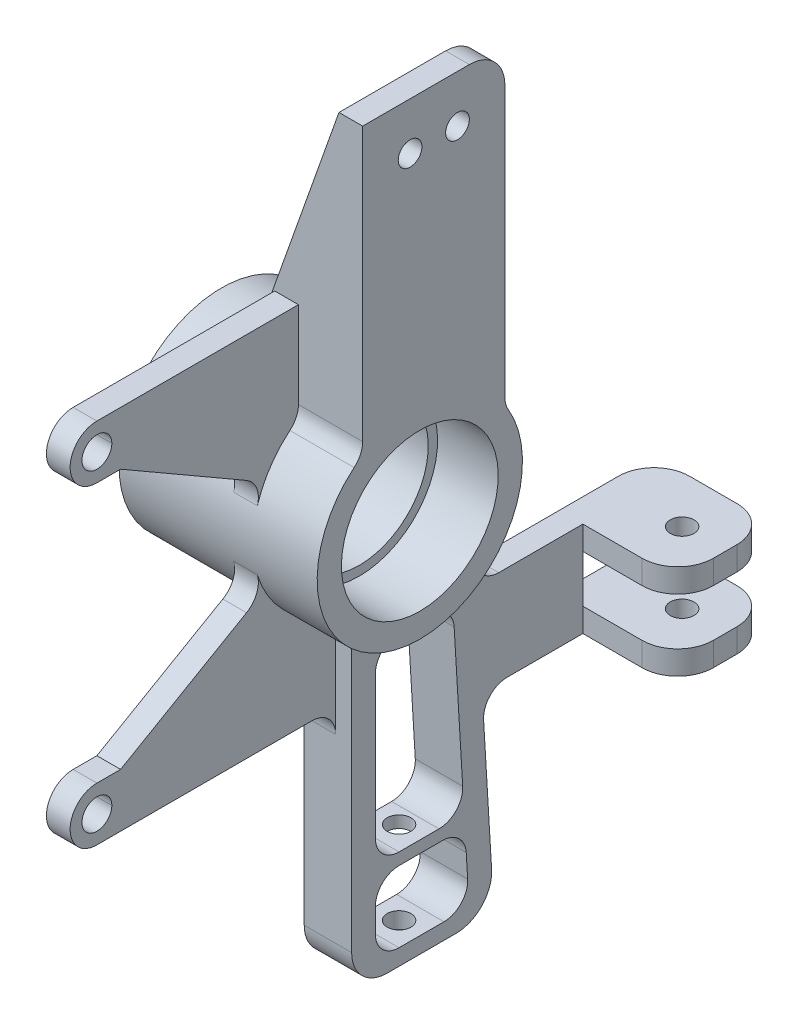
SolidWorks part; units mm, degrees
ref_plane "Front Plane" through (0, 0, 0) normal (0, 0, 1) x (1, 0, 0)
ref_plane "Top Plane" through (0, 0, 0) normal (0, 1, 0) x (1, 0, 0)
ref_plane "Right Plane" through (0, 0, 0) normal (1, 0, 0) x (0, 0, -1)
sketch "Sketch1" plane through (0, 0, 0) normal (0, 0, 1) x (1, 0, 0)
  line L0 (0, 0) -> (53.0908, 0) construction
  line L1 (0, 23.5) -> (16.2791, 23.5)
  line L2 (16.2791, 23.5) -> (16.2791, 18.5)
  line L3 (16.2791, 18.5) -> (36.8482, 18.5)
  line L4 (36.8482, 18.5) -> (36.8482, 21)
  line L5 (36.8482, 21) -> (53.0908, 21)
  line L6 (16.2791, 23.5) -> (16.2791, 0) construction
  line L7 (0, 23.5) -> (0, 0) construction
  line L8 (36.8482, 21) -> (36.8482, 0) construction
  line L9 (53.0908, 21) -> (53.0908, 0) construction
  line L10 (44.9695, 0) -> (61.4795, 0) construction
  line L11 (0, 11.75) -> (16.2791, 11.75) construction
  line L12 (36.8482, 10.5) -> (53.0908, 10.5) construction
  line L13 (0, 23.5) -> (0, 27.5)
  line L14 (0, 27.5) -> (53.0908, 27.5)
  line L15 (53.0908, 27.5) -> (53.0908, 21)
  point P11 (36.8482, 10.5)
  point P19 (8.1395, 11.75)
  point P20 (44.9695, 10.5)
  dimension "D1" = 21
  dimension "D2" = 23.5
  dimension "D3" = 16.2791
  dimension "D4" = 16.2426
  dimension "D5" = 36.83
  dimension "D6" = 4
  dimension "D7" = 2.5
  dimension "D8" = 16.51
revolve "Revolve1" add sketch "Sketch1" angle 360 about L0
sketch "Sketch2" plane through (53.0908, 0, 0) normal (1, 0, 0) x (0, 0, -1)
  line L0 (22.7917, 99.2079) -> (22.7917, 15.3879)
  line L1 (22.7917, 99.2079) -> (-15.3083, 99.2079)
  line L2 (-15.3083, 99.2079) -> (-15.3083, 22.8453)
  line L4 (-1525.5875, -203.2) -> (0, -203.2) construction
  circle A0 centre (0, 0) radius 27.5 construction
  arc A3 (22.7917, 15.3879) -> (-15.3083, 22.8453) centre (0, 0) ccw
  point P4 (3.7417, 99.2079)
  dimension "D1" = 83.82
  dimension "D2" = 38.1
extrude "Boss-Extrude1" add sketch "Sketch2" against normal blind 6.35
ref_plane "Plane1" through (33.8016, 0, 0) normal (1, 0, 0) x (0, 0, -1)
sketch "Sketch4" plane through (33.8016, 0, 0) normal (1, 0, 0) x (0, 0, -1)
  line L3 (0, 0) -> (13.7254, -101.6) construction
  line L4 (26.4254, -7.6125) -> (32.7754, -113.538)
  line L10 (-5.3246, -26.9796) -> (-5.3246, -113.538)
  line L15 (-5.3246, -113.538) -> (32.7754, -113.538)
  circle A0 centre (0, 0) radius 27.5 construction
  arc A1 (-5.3246, -26.9796) -> (26.4254, -7.6125) centre (0, 0) ccw
  point P3 (13.7254, -113.538)
  dimension "D1" = 11.938
  dimension "D2" = 38.1
  dimension "D7" = 31.75
extrude "Boss-Extrude2" add sketch "Sketch4" against normal blind 6.35 and the other way blind 6.35
sketch "Sketch5" plane through (40.1516, 0, 0) normal (1, 0, 0) x (0, 0, -1)
  line L0 (29.6234, -60.96) -> (82.0236, -60.96)
  line L2 (82.0236, -60.96) -> (82.0236, -54.61)
  line L3 (82.0236, -54.61) -> (56.6236, -54.61)
  line L4 (56.6236, -54.61) -> (56.6236, -41.91)
  line L5 (56.6236, -41.91) -> (82.0236, -41.91)
  line L6 (82.0236, -41.91) -> (82.0236, -35.56)
  line L7 (82.0236, -35.56) -> (28.1008, -35.56)
  line L9 (32.7754, -113.538) -> (26.4254, -7.6125) construction
  line L10 (28.1008, -35.56) -> (29.6234, -60.96)
  point P2 (69.3236, -54.61)
  point P10 (56.6236, -48.26)
  dimension "D1" = 6.35
  dimension "D2" = 25.4
  dimension "D3" = 12.7
extrude "Boss-Extrude3" add sketch "Sketch5" against normal blind 6.35
sketch "Sketch6" plane through (40.1516, 0, 0) normal (1, 0, 0) x (0, 0, -1)
  line L0 (82.0236, -54.61) -> (56.6236, -54.61) construction
  line L1 (82.0236, -35.56) -> (56.6236, -35.56)
  line L2 (82.0236, -35.56) -> (82.0236, -41.91)
  line L3 (82.0236, -41.91) -> (56.6236, -41.91)
  line L4 (56.6236, -35.56) -> (56.6236, -41.91)
  line L5 (82.0236, -60.96) -> (56.6236, -60.96)
  line L6 (82.0236, -60.96) -> (82.0236, -54.61)
  line L7 (82.0236, -54.61) -> (56.6236, -54.61)
  line L8 (56.6236, -60.96) -> (56.6236, -54.61)
  line L9 (56.6236, -54.61) -> (56.6236, -41.91) construction
extrude "Boss-Extrude4" add sketch "Sketch6" along normal blind 25.4
sketch "Sketch7" plane through (46.7408, 0, 0) normal (-1, 0, 0) x (0, 0, 1)
  line L0 (15.3083, 22.8453) -> (15.3083, 99.2079)
  line L1 (15.3083, 99.2079) -> (15.3083, 22.8453) construction
  line L2 (15.3083, 99.2079) -> (8.9583, 99.2079)
  line L3 (8.9583, 99.2079) -> (8.9583, 26)
  line L4 (-22.7917, 99.2079) -> (15.3083, 99.2079) construction
  circle A0 centre (0, 0) radius 27.5 construction
  arc A1 (15.3083, 22.8453) -> (-22.7917, 15.3879) centre (0, 0) ccw construction
  arc A2 (15.3083, 22.8453) -> (8.9583, 26) centre (0, 0) ccw
  dimension "D1" = 6.35
extrude "Boss-Extrude5" add sketch "Sketch7" along normal blind 25.4
sketch "Sketch8" plane through (35.8795, 0, 0) normal (-1, 0, 0) x (0, 0, 1)
  line L0 (15.3083, 22.8453) -> (15.3083, 99.2079) construction
  line L1 (15.3083, 49.175) -> (69.3, 49.175)
  line L4 (15.3083, 22.8453) -> (15.3083, 49.175)
  line L5 (69.3, 42) -> (76.475, 42) construction
  line L7 (24.4463, 12.5949) -> (62.95, 34.825)
  line L8 (62.95, 34.825) -> (69.3, 34.825)
  arc A0 (69.3, 38) -> (69.3, 46) centre (69.3, 42) ccw construction
  arc A1 (69.3, 46) -> (69.3, 38) centre (69.3, 42) ccw construction
  arc A2 (69.3, 38) -> (69.3, 46) centre (69.3, 42) ccw
  arc A3 (69.3, 46) -> (69.3, 38) centre (69.3, 42) ccw
  circle A4 centre (0, 0) radius 27.5 construction
  arc A6 (69.3, 34.825) -> (69.3, 49.175) centre (69.3, 42) ccw
  arc A14 (24.4463, 12.5949) -> (15.3083, 22.8453) centre (0, 0) ccw
  dimension "D1" = 3.175
  dimension "D2" = 30
  dimension "D3" = 6.35
extrude "Boss-Extrude6" add sketch "Sketch8" along normal blind 6.35
sketch "Sketch9" plane through (35.8795, 0, 0) normal (-1, 0, 0) x (0, 0, 1)
  line L0 (5.3246, -49.175) -> (69.3, -49.175)
  line L1 (5.3246, -26.9796) -> (5.3246, -113.538) construction
  line L3 (5.3246, -49.175) -> (5.3246, -26.9796)
  line L5 (69.3, -34.825) -> (62.95, -34.825)
  line L6 (62.95, -34.825) -> (24.4463, -12.5949)
  line L7 (69.3, -42) -> (76.475, -42) construction
  arc A0 (69.3, -46) -> (69.3, -38) centre (69.3, -42) ccw construction
  arc A1 (69.3, -38) -> (69.3, -46) centre (69.3, -42) ccw construction
  arc A2 (69.3, -46) -> (69.3, -38) centre (69.3, -42) ccw
  arc A3 (69.3, -38) -> (69.3, -46) centre (69.3, -42) ccw
  arc A4 (69.3, -49.175) -> (69.3, -34.825) centre (69.3, -42) ccw
  circle A5 centre (0, 0) radius 27.5 construction
  arc A7 (5.3246, -26.9796) -> (24.4463, -12.5949) centre (0, 0) ccw
  dimension "D1" = 3.175
  dimension "D3" = 6.35
  dimension "D2" = 30
sketch "Sketch10" plane through (0, 0, 8.9583) normal (0, 0, -1) x (-1, 0, 0)
  line L0 (-46.7408, 99.2079) -> (-21.3408, 27.5)
  line L1 (-21.3408, 99.2079) -> (-21.3408, 26) construction
  line L2 (-21.3408, 27.5) -> (-21.3408, 99.2079)
  line L3 (-21.3408, 99.2079) -> (-46.7408, 99.2079)
  line L4 (0, 27.5) -> (-53.0908, 27.5) construction
extrude "Cut-Extrude1" cut sketch "Sketch10" against normal up to next
sketch "Sketch13" plane through (40.1516, 0, 0) normal (1, 0, 0) x (0, 0, -1)
  line L0 (26.1551, -109.22) -> (25.0131, -90.17)
  line L1 (25.0131, -90.17) -> (1.0254, -90.17)
  line L2 (1.0254, -90.17) -> (1.0254, -109.22)
  line L3 (1.0254, -109.22) -> (26.1551, -109.22)
  line L4 (21.7774, -36.195) -> (24.8228, -86.995)
  line L5 (24.8228, -86.995) -> (1.0254, -86.995)
  line L6 (1.0254, -86.995) -> (1.0254, -36.195)
  line L7 (1.0254, -36.195) -> (21.7774, -36.195)
  line L8 (32.7754, -113.538) -> (29.6234, -60.96) construction
  line L9 (-5.3246, -26.9796) -> (-5.3246, -113.538) construction
  dimension "D1" = 6.35
  dimension "D2" = 6.35
  dimension "D3" = 3.175
  dimension "D4" = 7.62
  dimension "D5" = 19.05
  dimension "D6" = 50.8
extrude "Cut-Extrude2" cut sketch "Sketch13" against normal up to next
sketch "Sketch14" plane through (0, -86.995, 0) normal (0, 1, 0) x (1, 0, 0)
  circle A0 centre (33.8016, 13.7254) radius 3.175
  dimension "D1" = 6.35
extrude "Cut-Extrude3" cut sketch "Sketch14" against normal through all
sketch "Sketch15" plane through (53.0908, 0, 0) normal (1, 0, 0) x (0, 0, -1)
  line L0 (-2.6083, 86.5079) -> (10.0917, 86.5079) construction
  line L1 (22.7917, 99.2079) -> (-15.3083, 99.2079) construction
  circle A0 centre (-2.6083, 86.5079) radius 3.175
  circle A1 centre (10.0917, 86.5079) radius 3.175
  point P6 (3.7417, 99.2079)
  point P7 (3.7417, 86.5079)
  dimension "D1" = 6.35
  dimension "D3" = 12.7
  dimension "D2" = 12.7
extrude "Cut-Extrude4" cut sketch "Sketch15" against normal up to next
sketch "Sketch16" plane through (0, -35.56, 0) normal (0, 1, 0) x (1, 0, 0)
  circle A0 centre (54.033, 69.3236) radius 3.175
  dimension "D1" = 6.35
extrude "Cut-Extrude5" cut sketch "Sketch16" against normal through all
extrude "Boss-Extrude7" add sketch "Sketch9" along normal blind 6.35
fillet "0.375 Fillet1" radius 9.525 9 edges at (33.8016, -113.538, 5.3246) (33.8016, -113.538, -32.7754) (49.9158, 99.2079, -22.7917) (65.5516, -57.785, -82.0236) (65.5516, -57.785, -56.6236) (65.5516, -38.735, -56.6236) (65.5516, -38.735, -82.0236) (33.8016, -57.785, -82.0236) (33.8016, -38.735, -82.0236)
fillet "0.25 Fillet1" radius 6.35 18 edges at (36.9766, -60.96, -29.6234) (36.9766, -35.56, -28.1008) (34.0408, 26, 8.9583) (33.8016, -7.6125, -26.4254) (49.9158, 15.3879, -22.7917) (44.4852, 22.8453, 15.3083) (25.4352, 22.8453, 15.3083) (32.7045, 12.5949, 24.4463) (32.7045, -12.5949, 24.4463) (32.7045, -49.175, 5.3246) (33.8016, -36.195, -1.0254) (33.8016, -36.195, -21.7774) (33.8016, -86.995, -1.0254) (33.8016, -86.995, -24.8228) (33.8016, -109.22, -26.1551) (33.8016, -109.22, -1.0254) (33.8016, -90.17, -1.0254) (33.8016, -90.17, -25.0131)
ref_plane "bottom brake hole plane" through (0, -42, 0) normal (0, 1, 0) x (1, 0, 0)
ref_plane "top brake hole plane" through (0, 42, 0) normal (0, 1, 0) x (1, 0, 0)
split line "Split Line1"
split line "Split Line2"
